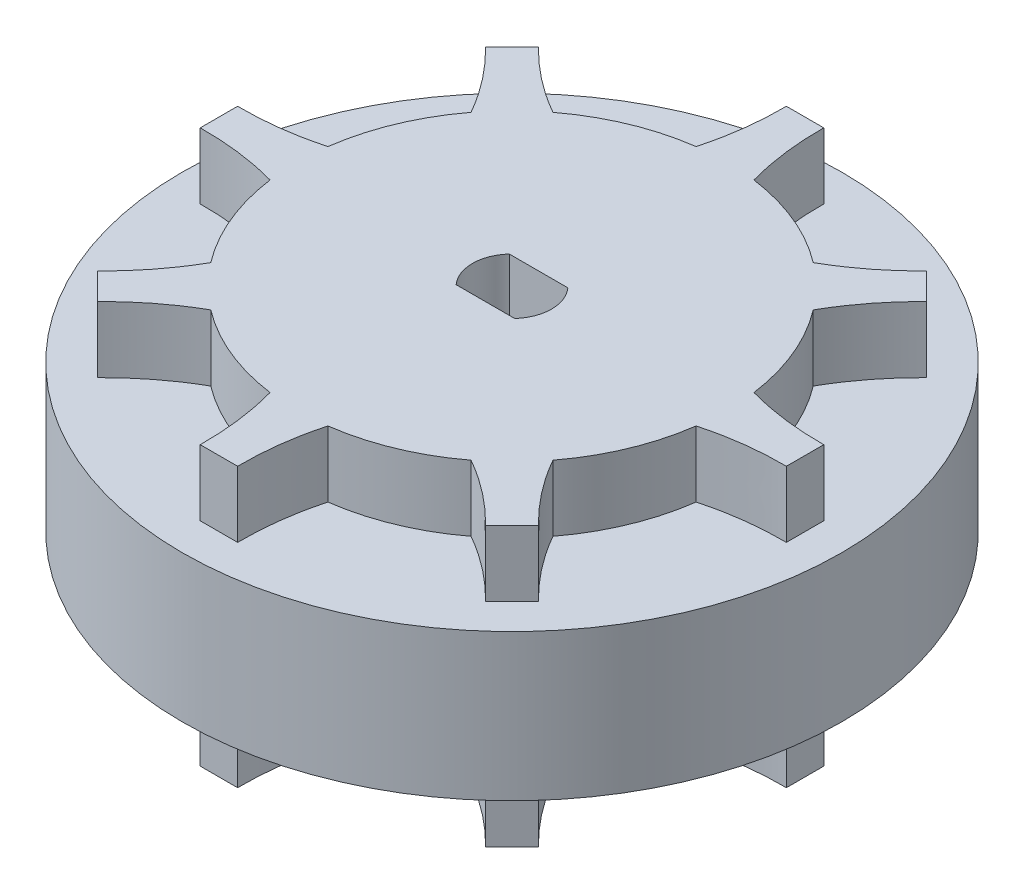
SolidWorks part; units mm, degrees
ref_plane "Front Plane" through (0, 0, 0) normal (0, 0, 1) x (1, 0, 0)
ref_plane "Top Plane" through (0, 0, 0) normal (0, 1, 0) x (1, 0, 0)
ref_plane "Right Plane" through (0, 0, 0) normal (1, 0, 0) x (0, 0, -1)
sketch "Sketch1" plane through (0, 0, 0) normal (0, 1, 0) x (1, 0, 0)
  line L0 (0, 20.9267) -> (0, -30.1304) construction
  line L1 (-41.7081, 0) -> (48.7066, 0) construction
  line L2 (0, 0) -> (-17.0459, 17.0459) construction
  line L3 (0, 0) -> (17.2274, -17.2274) construction
  line L4 (-15.0438, 13.2405) -> (-13.2405, 15.0438)
  line L6 (-6.1062, 10.3817) -> (-10.3817, 6.1062)
  line L8 (-1.2752, 20) -> (1.2752, 20)
  line L9 (3.0232, 11.6587) -> (-3.0232, 11.6587)
  line L10 (13.2405, 15.0438) -> (15.0438, 13.2405)
  line L11 (10.3817, 6.1062) -> (6.1062, 10.3817)
  line L12 (20, 1.2752) -> (20, -1.2752)
  line L13 (11.6587, -3.0232) -> (11.6587, 3.0232)
  line L14 (15.0438, -13.2405) -> (13.2405, -15.0438)
  line L15 (6.1062, -10.3817) -> (10.3817, -6.1062)
  line L16 (1.2752, -20) -> (-1.2752, -20)
  line L17 (-3.0232, -11.6587) -> (3.0232, -11.6587)
  line L18 (-13.2405, -15.0438) -> (-15.0438, -13.2405)
  line L19 (-10.3817, -6.1062) -> (-6.1062, -10.3817)
  line L20 (-20, -1.2752) -> (-20, 1.2752)
  line L21 (-11.6587, 3.0232) -> (-11.6587, -3.0232)
  circle A0 centre (0, 0) radius 14.6695
  spline S0 degree 2 poles (-15.0438, 13.2405) (-11.905, 10.1654) (-10.3817, 6.1062) knots 0 0 0 1 1 1
  spline S1 degree 2 poles (-13.2405, 15.0438) (-10.1654, 11.905) (-6.1062, 10.3817) knots 0 0 0 1 1 1
  spline S2 degree 2 poles (-1.2752, 20) (-1.2301, 15.6061) (-3.0232, 11.6587) knots 0 0 0 1 1 1
  spline S3 degree 2 poles (1.2752, 20) (1.2301, 15.6061) (3.0232, 11.6587) knots 0 0 0 1 1 1
  spline S4 degree 2 poles (13.2405, 15.0438) (10.1654, 11.905) (6.1062, 10.3817) knots 0 0 0 1 1 1
  spline S5 degree 2 poles (15.0438, 13.2405) (11.905, 10.1654) (10.3817, 6.1062) knots 0 0 0 1 1 1
  spline S6 degree 2 poles (20, 1.2752) (15.6061, 1.2301) (11.6587, 3.0232) knots 0 0 0 1 1 1
  spline S7 degree 2 poles (20, -1.2752) (15.6061, -1.2301) (11.6587, -3.0232) knots 0 0 0 1 1 1
  spline S8 degree 2 poles (15.0438, -13.2405) (11.905, -10.1654) (10.3817, -6.1062) knots 0 0 0 1 1 1
  spline S9 degree 2 poles (13.2405, -15.0438) (10.1654, -11.905) (6.1062, -10.3817) knots 0 0 0 1 1 1
  spline S10 degree 2 poles (1.2752, -20) (1.2301, -15.6061) (3.0232, -11.6587) knots 0 0 0 1 1 1
  spline S11 degree 2 poles (-1.2752, -20) (-1.2301, -15.6061) (-3.0232, -11.6587) knots 0 0 0 1 1 1
  spline S12 degree 2 poles (-13.2405, -15.0438) (-10.1654, -11.905) (-6.1062, -10.3817) knots 0 0 0 1 1 1
  spline S13 degree 2 poles (-15.0438, -13.2405) (-11.905, -10.1654) (-10.3817, -6.1062) knots 0 0 0 1 1 1
  spline S14 degree 2 poles (-20, -1.2752) (-15.6061, -1.2301) (-11.6587, -3.0232) knots 0 0 0 1 1 1
  spline S15 degree 2 poles (-20, 1.2752) (-15.6061, 1.2301) (-11.6587, 3.0232) knots 0 0 0 1 1 1
  point P60 (0, 0)
  dimension "D1" = 20
  dimension "D2" = 8
extrude "Boss-Extrude2" add sketch "Sketch1" along normal blind 19 contours S1 L4 S0 A0 | S1 A0 S0 L6 | S3 A0 S2 L9 | S3 L8 S2 A0 | S5 A0 S4 L11 | S5 L10 S4 A0 | S7 A0 S6 L13 | S7 L12 S6 A0 | S9 L14 S8 A0 | S9 A0 S8 L15 | S11 L16 S10 A0 | S11 A0 S10 L17 | S13 L18 S12 A0 | S13 A0 S12 L19 | S15 A0 S14 L21 | S15 L20 S14 A0 | A0 S15 L21 S14 S13 L19 S12 S11 L17 S10 S9 L15 S8 S7 L13 S6 S5 L11 S4 S3 L9 S2 S1 L6 S0 region at (-12.0988, 0, -12.0988) region at (0, 0, 0) region at (-9.2165, 0, -9.2165) region at (-13.034, 0, 0) region at (-17.1103, 0, 0) region at (0, 0, -17.1103) region at (0, 0, -13.034) region at (-9.2165, 0, 9.2165) region at (-12.0988, 0, 12.0988) region at (12.0988, 0, -12.0988) region at (9.2165, 0, -9.2165) region at (0, 0, 13.034) region at (0, 0, 17.1103) region at (17.1103, 0, 0) region at (13.034, 0, 0) region at (9.2165, 0, 9.2165) region at (12.0988, 0, 12.0988)
sketch "Sketch3" plane through (0, 19, 0) normal (0, 1, 0) x (1, 0, 0)
  circle A0 centre (0, 0) radius 22.5
  dimension "D1" = 45
extrude "Boss-Extrude3" add sketch "Sketch3" against normal blind 10 from offset 4.5 offset against normal yes
sketch "Sketch4" plane through (0, 19, 0) normal (0, 1, 0) x (1, 0, 0)
  line L0 (-2, 1.8138) -> (2, 1.8138)
  line L1 (-7.3468, 0) -> (6.249, 0) construction
  line L2 (-2, -1.8138) -> (2, -1.8138)
  arc A0 (-2, 1.8138) -> (-2, -1.8138) centre (0, 0) ccw
  arc A1 (2, -1.8138) -> (2, 1.8138) centre (0, 0) ccw
  dimension "D1" = 5.4
  dimension "D2" = 4
extrude "Cut-Extrude1" cut sketch "Sketch4" against normal up to surface (19 mm away) up to face at (0, 0, 0)
